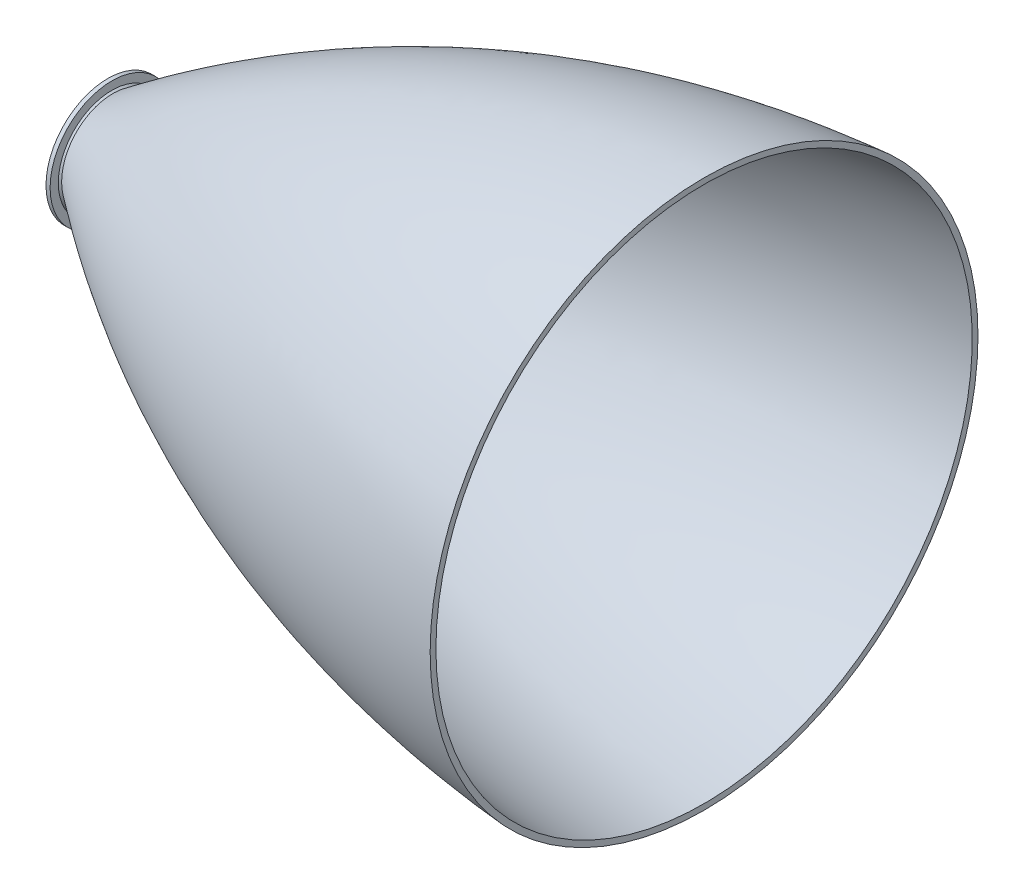
SolidWorks part; units mm, degrees
material "A286 Iron Base Superalloy"
ref_plane "Front Plane" through (0, 0, 0) normal (0, 0, 1) x (1, 0, 0)
ref_plane "Top Plane" through (0, 0, 0) normal (0, 1, 0) x (1, 0, 0)
ref_plane "Right Plane" through (0, 0, 0) normal (1, 0, 0) x (0, 0, -1)
sketch "Sketch1" plane through (0, 0, 0) normal (0, 0, 1) x (1, 0, 0)
  line L0 (-1229.8282, 0) -> (1426.3964, 0) construction
  line L1 (0, -70.104) -> (0, 70.104) construction
  line L2 (0, 0) -> (914.4, 0) construction
  line L3 (914.4, -414.655) -> (914.4, 414.655) construction
  line L5 (914.4, 423.545) -> (914.4, 414.655)
  line L6 (0, -78.994) -> (0, -70.104)
  line L7 (914.4, -423.545) -> (914.4, -414.655)
  line L8 (-412.8242, -144.8099) -> (-412.8242, 144.8099) construction
  line L9 (-412.8242, 144.8099) -> (-412.8242, 153.6999)
  line L10 (-412.8242, -144.8099) -> (-412.8242, -153.6999)
  spline S0 degree 2 poles (0, 70.104) (420.1673, 366.6312) (914.4, 414.655) knots 0 0 0 1 1 1
  spline S1 degree 2 poles (0, -70.104) (420.1673, -366.6312) (914.4, -414.655) knots 0 0 0 1 1 1
  spline S2 degree 2 poles (0, -78.994) (408.2901, -383.6129) (914.4, -423.545) knots 0 0 0 1 1 1
  spline S3 degree 2 poles (0, -70.104) (420.1673, -366.6312) (914.4, -414.655) knots 0 0 0 1 1 1
  spline S4 degree 2 poles (0, 78.994) (408.2901, 383.6129) (914.4, 423.545) knots 0 0 0 1 1 1
  spline S5 degree 2 poles (0, 70.104) (-195.4497, 157.4108) (-412.8242, 144.8099) knots 0 0 0 1 1 1
  spline S6 degree 2 poles (0, -70.104) (-195.4497, -157.4108) (-412.8242, -144.8099) knots 0 0 0 1 1 1
  spline S7 degree 2 poles (0, -78.994) (-192.7304, -176.7061) (-412.8242, -153.6999) knots 0 0 0 1 1 1
  spline S9 degree 2 poles (0, 78.994) (-192.7304, 176.7061) (-412.8242, 153.6999) knots 0 0 0 1 1 1
  point P8 (0, 0)
  point P14 (914.4, 0)
  point P22 (-412.8242, 0)
  dimension "D4" = 8.89
  dimension "D1" = 140.208
  dimension "D2" = 914.4
  dimension "D3" = 829.31
  dimension "D5" = 8.89
  dimension "D6" = 8.89
  dimension "D7" = 289.6197
revolve "Revolve3" add sketch "Sketch1" angle 360 about L0 region at (900.6652, 419.1, 0)
ref_plane "Plane1" through (0, 0, 0) normal (1, 0, 0) x (0, 0, -1)
ref_plane "Plane2" through (-7.62, 0, 0) normal (-1, 0, 0) x (0, 0, 1)
sketch "Sketch4" plane through (-7.62, 0, 0) normal (-1, 0, 0) x (0, 0, 1)
  line L1 (-1213.2286, 638.9142) -> (1085.9115, 638.9142)
  line L2 (-1213.2286, 638.9142) -> (-1213.2286, -445.9528)
  line L3 (-1213.2286, -445.9528) -> (1085.9115, -445.9528)
  line L4 (1085.9115, 638.9142) -> (1085.9115, -445.9528)
extrude "Cut-Extrude1" cut sketch "Sketch4" along normal blind 554.228
sketch "Sketch5" plane through (-7.62, 0, 0) normal (-1, 0, 0) x (0, 0, 1)
  circle A0 centre (0, 0) radius 95.5048
  circle A1 centre (0, 0) radius 82.8048 construction
  circle A2 centre (0, 0) radius 82.8048
  dimension "D1" = 12.7
extrude "Boss-Extrude1" add sketch "Sketch5" against normal blind 6.35 separate body
